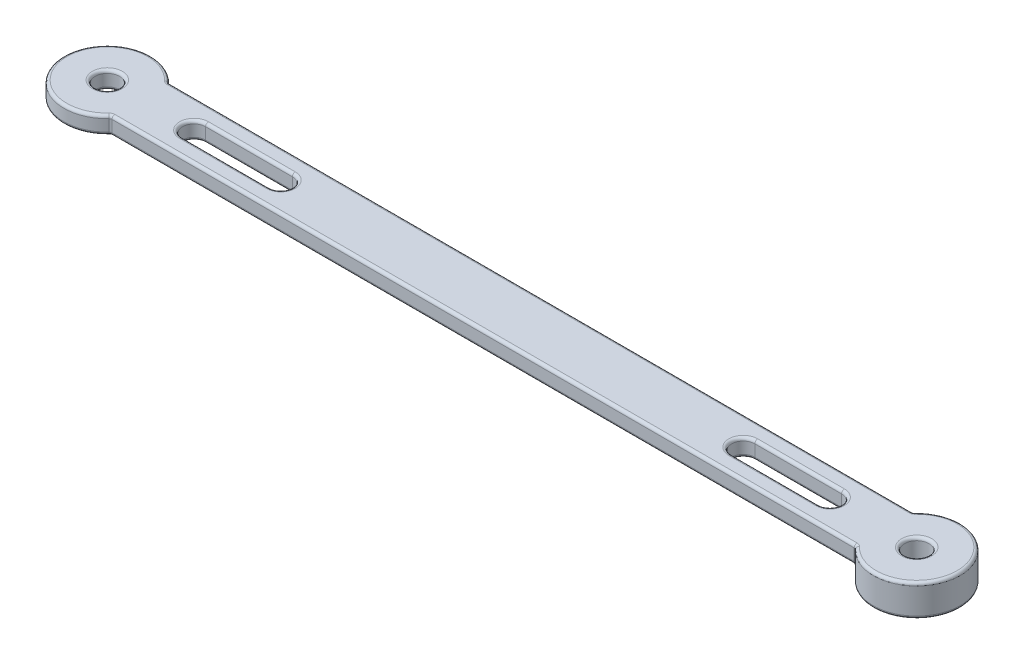
SolidWorks part; units mm, degrees
ref_plane "Front Plane" through (0, 0, 0) normal (0, 0, 1) x (1, 0, 0)
ref_plane "Top Plane" through (0, 0, 0) normal (0, 1, 0) x (1, 0, 0)
ref_plane "Right Plane" through (0, 0, 0) normal (1, 0, 0) x (0, 0, -1)
sketch "Sketch1" plane through (0, 0, 0) normal (0, 1, 0) x (1, 0, 0)
  line L0 (5.5902, 5) -> (134.4098, 5)
  line L1 (5.5902, -5) -> (134.4098, -5)
  circle A0 centre (0, 0) radius 2.1
  circle A1 centre (140, 0) radius 2.1
  arc A2 (5.5902, 5) -> (5.5902, -5) centre (0, 0) ccw
  arc A3 (134.4098, -5) -> (134.4098, 5) centre (140, 0) ccw
  dimension "D1" = 4.2
  dimension "D2" = 4.2
  dimension "D4" = 15
  dimension "D5" = 15
  dimension "D3" = 140
  dimension "D6" = 5
  dimension "D7" = 10
extrude "Boss-Extrude1" add sketch "Sketch1" along normal blind 3
sketch "Sketch2" plane through (0, 0, 0) normal (0, -1, 0) x (1, 0, 0)
  circle A0 centre (140, 0) radius 7.5
  circle A1 centre (140, 0) radius 2.1
  dimension "D1" = 4.2
  dimension "D2" = 15
extrude "Boss-Extrude2" add sketch "Sketch2" along normal blind 2.5
sketch "Sketch3" plane through (0, 3, 0) normal (0, 1, 0) x (1, 0, 0)
  line L0 (15, 0) -> (30, 0) construction
  line L1 (70, 5) -> (70, -5) construction
  line L2 (15, 2) -> (30, 2)
  line L3 (15, -2) -> (30, -2)
  line L4 (134.4098, 5) -> (5.5902, 5) construction
  line L5 (5.5902, -5) -> (134.4098, -5) construction
  line L6 (125, 0) -> (110, 0) construction
  line L7 (125, 2) -> (110, 2)
  line L8 (125, -2) -> (110, -2)
  arc A0 (15, 2) -> (15, -2) centre (15, 0) ccw
  arc A1 (30, -2) -> (30, 2) centre (30, 0) ccw
  arc A2 (125, 2) -> (125, -2) centre (125, 0) cw
  arc A3 (110, -2) -> (110, 2) centre (110, 0) cw
  point P5 (22.5, 0)
  point P16 (117.5, 0)
  dimension "D1" = 2
  dimension "D2" = 15
  dimension "D3" = 15
extrude "Cut-Extrude1" cut sketch "Sketch3" against normal blind 6
fillet "Fillet1" radius 0.5 33 edges at (70, 0, 5) (70, 3, 5) (13, 0, 0) (22.5, 0, -2) (32, 0, 0) (13, 3, 0) (22.5, 3, -2) (32, 3, 0) (108, 0, 0) (117.5, 0, -2) (127, 0, 0) (108, 3, 0) (117.5, 3, -2) (127, 3, 0) (-7.5, 3, 0) (5.5902, 1.5, 5) (-7.5, 0, 0) (140, -2.5, -7.5) (147.5, 3, 0) (132.5, 0, 0) (134.4098, 1.5, 5) (140, -2.5, -2.1) (140, 3, 2.1) (0, 0, 2.1) (0, 3, 2.1) (134.4098, 1.5, -5) (70, 3, -5) (5.5902, 1.5, -5) (70, 0, -5) (22.5, 0, 2) (22.5, 3, 2) (117.5, 0, 2) (117.5, 3, 2)
